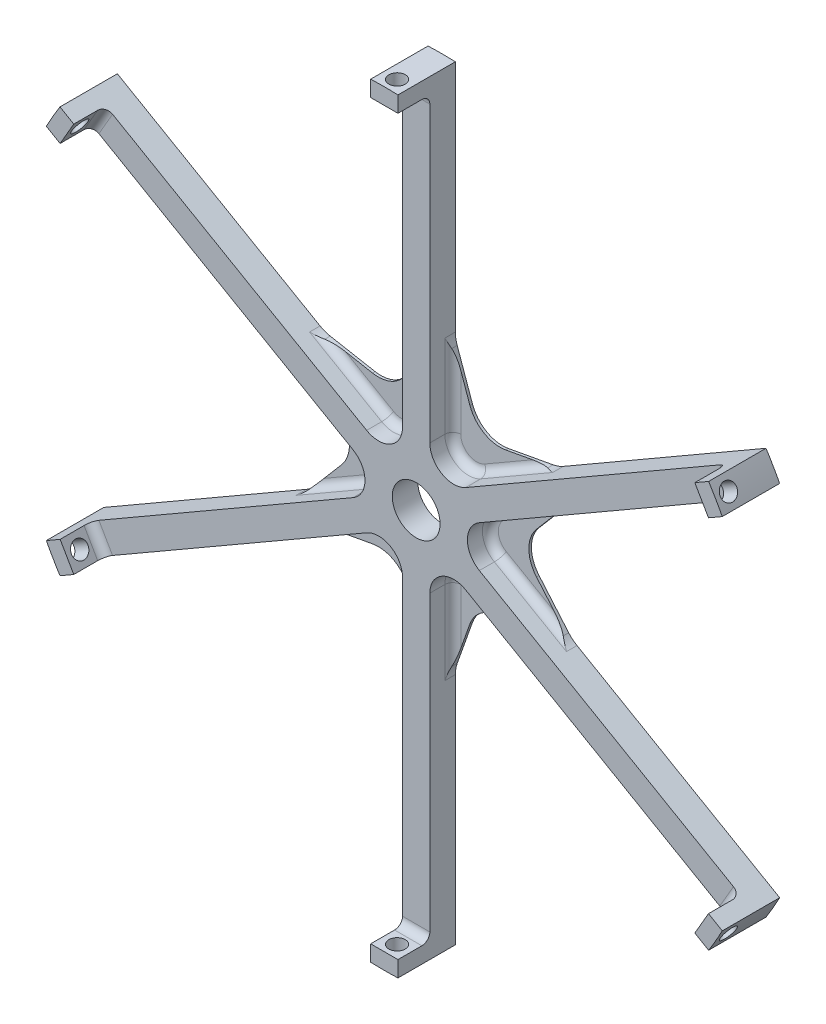
SolidWorks part; units mm, degrees
material "6061-T6 (SS)"
ref_plane "Front" through (0, 0, 0) normal (0, 0, 1) x (1, 0, 0)
ref_plane "Top" through (0, 0, 0) normal (0, 1, 0) x (1, 0, 0)
ref_plane "Right" through (0, 0, 0) normal (1, 0, 0) x (0, 0, -1)
sketch "Sketch1" plane through (0, 0, 0) normal (0, 0, 1) x (1, 0, 0)
  circle A0 centre (0, 0) radius 76.2
  dimension "D1" = 152.4
extrude "Boss-Extrude1" add sketch "Sketch1" along normal blind 11.43
sketch "Sketch3" plane through (0, 0, 11.43) normal (0, 0, 1) x (1, 0, 0)
  circle A0 centre (0, 0) radius 4.7625
  dimension "D1" = 9.525
extrude "Cut-Extrude2" cut sketch "Sketch3" against normal through all
sketch "Sketch2" plane through (0, 0, 11.43) normal (0, 0, 1) x (1, 0, 0)
  line L0 (0, 0) -> (0, 76.2) construction
  line L1 (0, 0) -> (-65.9911, 38.1) construction
  line L2 (-2.7178, 12.9563) -> (-2.7178, 76.2)
  line L3 (-9.8615, 8.8318) -> (-64.6322, 40.4537)
  line L4 (2.7178, -4.7074) -> (2.7178, 76.2)
  line L5 (2.7178, -4.7074) -> (-67.35, 35.7463)
  line L6 (-2.7178, 4.7074) -> (-2.7178, 76.2) construction
  line L7 (-2.7178, 4.7074) -> (-64.6322, 40.4537) construction
  circle A0 centre (0, 0) radius 76.2 construction
  circle A1 centre (0, 0) radius 7.9375
  arc A2 (-2.7178, 12.9563) -> (-9.8615, 8.8318) centre (-7.4803, 12.9563) cw
  circle M1 centre (0, 0) radius 76.2
  dimension "D1" = 15.875
  dimension "D5" = 4.7625
  dimension "D2" = 60
  dimension "D3" = 2.7178
  dimension "D4" = 2.7178
extrude "Cut-Extrude1" cut sketch "Sketch2" against normal through all contours A1 L2 L3 M1 region at (-25.4311, 44.0479, 11.43)
pattern_circular "CirPattern1" count 6 over 360 about axis through (0, 0, 11.43) along (0, 0, -1) of "Cut-Extrude1"
sketch "Sketch4" plane through (0, 0, 11.43) normal (0, 0, 1) x (1, 0, 0)
  line L0 (0, 0) -> (0, 73.025) construction
  line L1 (-9.8615, 8.8318) -> (-64.5902, 40.4294) construction
  line L2 (-12.5793, 4.1244) -> (-67.308, 35.7221) construction
  line L3 (-2.7178, 12.9563) -> (-2.7178, 76.1515) construction
  line L4 (2.7178, 12.9563) -> (2.7178, 76.1515) construction
  line L5 (9.8615, 8.8318) -> (64.5902, 40.4294) construction
  line L6 (12.5793, 4.1244) -> (67.308, 35.7221) construction
  line L7 (2.7178, -12.9563) -> (2.7178, -76.1515) construction
  line L8 (-9.8616, -8.8318) -> (-64.5902, -40.4294) construction
  line L9 (-12.5794, -4.1244) -> (-67.308, -35.7221) construction
  line L10 (-2.7178, -12.9563) -> (-2.7178, -76.1515) construction
  line L11 (9.8615, -8.8318) -> (64.5902, -40.4294) construction
  line L12 (12.5793, -4.1244) -> (67.308, -35.7221) construction
  line L13 (-9.8615, 8.8318) -> (-64.5902, 40.4294)
  line L14 (-12.5793, 4.1244) -> (-67.308, 35.7221)
  line L15 (-2.7178, 12.9563) -> (-2.7178, 76.1515)
  line L16 (2.7178, 12.9563) -> (2.7178, 76.1515)
  line L17 (9.8615, 8.8318) -> (64.5902, 40.4294)
  line L18 (12.5793, 4.1244) -> (67.308, 35.7221)
  line L19 (2.7178, -12.9563) -> (2.7178, -76.1515)
  line L20 (-9.8616, -8.8318) -> (-64.5902, -40.4294)
  line L21 (-12.5794, -4.1244) -> (-67.308, -35.7221)
  line L22 (-2.7178, -12.9563) -> (-2.7178, -76.1515)
  line L23 (9.8615, -8.8318) -> (64.5902, -40.4294)
  line L24 (12.5793, -4.1244) -> (67.308, -35.7221)
  line L25 (2.7178, 72.9744) -> (-2.7178, 72.9744)
  line L26 (-61.8388, 38.8409) -> (-64.5566, 34.1335)
  line L27 (-64.5566, -34.1335) -> (-61.8388, -38.8409)
  line L28 (-2.7178, -72.9744) -> (2.7178, -72.9744)
  line L29 (61.8388, -38.8409) -> (64.5566, -34.1335)
  line L30 (61.8388, 38.8409) -> (64.5566, 34.1335)
  circle A0 centre (0, 0) radius 73.025
  line M4 (-12.5794, -4.1244) -> (-67.308, -35.7221)
  line M8 (-2.7178, -12.9563) -> (-2.7178, -76.1515)
  line M12 (9.8615, -8.8318) -> (64.5902, -40.4294)
  line M16 (12.5793, 4.1244) -> (67.308, 35.7221)
  line M20 (2.7178, 12.9563) -> (2.7178, 76.1515)
  line M24 (-9.8615, 8.8318) -> (-64.5902, 40.4294)
  circle M26 centre (0, 0) radius 4.7625
  dimension "D1" = 146.05
extrude "Cut-Extrude3" cut sketch "Sketch4" against normal blind 6.35 contours L25 L15 L26 L14 L27 L20 L28 L19 L29 L24 L30 L17 M26 M24 M4 M8 M12 M16 M20 region at (35.4801, 61.4534, 11.43)
hole_wizard "#30 (0.1285) Diameter Hole1" positions "3DSketch1" profile "Sketch5" hole size "#30" standard "ANSI Inch"
sketch3d "3DSketch1"
  point P0 (0, 76.2, 8.89)
  dimension "D1" = 2.54
sketch "Sketch5" plane through (0, 76.2, 8.89) normal (1, 0, 0) x (0, 0, 1)
  line L0 (0, 0) -> (0, 39.0806)
  line L1 (0, 39.0806) -> (1.6319, 38.1)
  line L2 (1.6319, 38.1) -> (1.6319, 0)
  line L5 (1.6319, 0) -> (0, 0)
  line L10 (0, 39.0806) -> (-1.632, 38.1) construction
  line L11 (0, -6.35) -> (0, 107.95) construction
  dimension "Hole Dia." = 3.2639
  dimension "Hole Depth" = 38.1
  dimension "Drill Angle" = 118
pattern_circular "CirPattern2" count 6 over 360 about axis through (0, 0, 11.43) along (0, 0, -1) of "#30 (0.1285) Diameter Hole1"
fillet "Fillet3" radius 1.5875 6 edges at (-63.1977, 36.4872, 5.08) (0, 72.9744, 5.08) (63.1977, 36.4872, 5.08) (63.1977, -36.4872, 5.08) (0, -72.9744, 5.08) (-63.1977, -36.4872, 5.08)
sketch "Sketch7" plane through (0, 0, 0) normal (0, 0, -1) x (-1, 0, 0)
  line L0 (-12.5793, 4.1244) -> (-67.308, 35.7221) construction
  line L1 (-12.5793, -4.1244) -> (-67.308, -35.7221) construction
  line L2 (-25.9934, -11.869) -> (-15.875, 0)
  line L3 (-15.875, 0) -> (-25.9934, 11.869)
  line L4 (-9.8615, -8.8318) -> (-64.5902, -40.4294) construction
  line L5 (-2.7178, -12.9563) -> (-2.7178, -76.1515) construction
  line L6 (2.7178, -12.9563) -> (2.7178, -76.1515) construction
  line L7 (9.8616, -8.8318) -> (64.5902, -40.4294) construction
  line L8 (-12.5793, -4.1244) -> (-67.308, -35.7221)
  line L9 (-12.5793, 4.1244) -> (-67.308, 35.7221)
  line L10 (12.5794, -4.1244) -> (67.308, -35.7221) construction
  line L11 (12.5793, 4.1244) -> (67.308, 35.7221) construction
  line L12 (9.8615, 8.8318) -> (64.5902, 40.4294) construction
  line L13 (2.7178, 12.9563) -> (2.7178, 76.1515) construction
  line L14 (-2.7178, 12.9563) -> (-2.7178, 76.1515) construction
  line L15 (-9.8615, 8.8318) -> (-64.5902, 40.4294) construction
  line L16 (-9.8615, -8.8318) -> (-64.5902, -40.4294)
  line L17 (-2.7178, -12.9563) -> (-2.7178, -76.1515)
  line L18 (2.7178, -12.9563) -> (2.7178, -76.1515)
  line L19 (9.8616, -8.8318) -> (64.5902, -40.4294)
  line L20 (12.5794, -4.1244) -> (67.308, -35.7221)
  line L21 (12.5793, 4.1244) -> (67.308, 35.7221)
  line L22 (9.8615, 8.8318) -> (64.5902, 40.4294)
  line L23 (2.7178, 12.9563) -> (2.7178, 76.1515)
  line L24 (-2.7178, 12.9563) -> (-2.7178, 76.1515)
  line L25 (-9.8615, 8.8318) -> (-64.5902, 40.4294)
  line L26 (0, 0) -> (-37.8206, 0) construction
  line L27 (0, 0) -> (-18.9103, 32.7536) construction
  line L28 (0, 0) -> (18.9103, 32.7536) construction
  line L29 (0, 0) -> (37.8206, 0) construction
  line L30 (0, 0) -> (18.9103, -32.7536) construction
  line L31 (0, 0) -> (-18.9103, -32.7536) construction
  line L32 (-23.2756, -16.5764) -> (-7.9375, -13.7482)
  line L33 (-7.9375, -13.7482) -> (-2.7178, -28.4455)
  line L34 (-23.2756, 16.5764) -> (-7.9375, 13.7482)
  line L35 (-7.9375, 13.7482) -> (-2.7178, 28.4455)
  line L36 (2.7178, 28.4455) -> (7.9375, 13.7482)
  line L37 (7.9375, 13.7482) -> (23.2756, 16.5764)
  line L38 (25.9934, 11.869) -> (15.875, 0)
  line L39 (15.875, 0) -> (25.9934, -11.869)
  line L40 (23.2756, -16.5764) -> (7.9375, -13.7482)
  line L41 (7.9375, -13.7482) -> (2.7178, -28.4455)
  circle A0 centre (0, 0) radius 28.575
  circle A1 centre (0, 0) radius 4.7625
  arc A2 (2.7178, 12.9563) -> (9.8615, 8.8318) centre (7.4803, 12.9563) ccw construction
  arc A3 (12.5793, 4.1244) -> (12.5794, -4.1244) centre (14.9606, 0) ccw construction
  arc A4 (9.8616, -8.8318) -> (2.7178, -12.9563) centre (7.4803, -12.9563) ccw construction
  arc A5 (-2.7178, -12.9563) -> (-9.8615, -8.8318) centre (-7.4803, -12.9563) ccw construction
  arc A6 (-12.5793, -4.1244) -> (-12.5793, 4.1244) centre (-14.9606, 0) ccw construction
  arc A7 (-9.8615, 8.8318) -> (-2.7178, 12.9563) centre (-7.4803, 12.9563) ccw construction
  circle A8 centre (0, 0) radius 15.875
  arc A14 (-9.8615, 8.8318) -> (-2.7178, 12.9563) centre (-7.4803, 12.9563) ccw
  arc A15 (-12.5793, -4.1244) -> (-12.5793, 4.1244) centre (-14.9606, 0) ccw
  arc A16 (-2.7178, -12.9563) -> (-9.8615, -8.8318) centre (-7.4803, -12.9563) ccw
  arc A17 (9.8616, -8.8318) -> (2.7178, -12.9563) centre (7.4803, -12.9563) ccw
  arc A18 (12.5793, 4.1244) -> (12.5794, -4.1244) centre (14.9606, 0) ccw
  arc A19 (2.7178, 12.9563) -> (9.8615, 8.8318) centre (7.4803, 12.9563) ccw
  point P47 (0, 0)
  line M2 (67.308, -35.7221) -> (12.5794, -4.1244)
  arc M3 (12.5794, -4.1244) -> (12.5793, 4.1244) centre (14.9606, 0) cw
  line M4 (12.5793, 4.1244) -> (67.308, 35.7221)
  line M6 (64.5902, 40.4294) -> (9.8615, 8.8318)
  arc M7 (9.8615, 8.8318) -> (2.7178, 12.9563) centre (7.4803, 12.9563) cw
  line M8 (2.7178, 12.9563) -> (2.7178, 76.1515)
  line M10 (-2.7178, 76.1515) -> (-2.7178, 12.9563)
  arc M11 (-2.7178, 12.9563) -> (-9.8615, 8.8318) centre (-7.4803, 12.9563) cw
  line M12 (-9.8615, 8.8318) -> (-64.5902, 40.4294)
  line M14 (-67.308, 35.7221) -> (-12.5793, 4.1244)
  arc M15 (-12.5793, 4.1244) -> (-12.5793, -4.1244) centre (-14.9606, 0) cw
  line M16 (-12.5793, -4.1244) -> (-67.308, -35.7221)
  line M18 (-64.5902, -40.4294) -> (-9.8615, -8.8318)
  arc M19 (-9.8615, -8.8318) -> (-2.7178, -12.9563) centre (-7.4803, -12.9563) cw
  line M20 (-2.7178, -12.9563) -> (-2.7178, -76.1515)
  line M22 (2.7178, -76.1515) -> (2.7178, -12.9563)
  arc M23 (2.7178, -12.9563) -> (9.8616, -8.8318) centre (7.4803, -12.9563) cw
  line M24 (9.8616, -8.8318) -> (64.5902, -40.4294)
  dimension "D1" = 57.15
  dimension "D2" = 31.75
  dimension "D3" = 6
extrude "Boss-Extrude2" add sketch "Sketch7" against normal blind 0.508 contours A8 L22 L37 | A8 L36 L23 | A8 M6 M8 M7 | A8 M4 M3 M2 | A8 L38 L21 | A8 L20 L39 | A8 L40 L19 | A8 M22 M24 M23 | A8 L18 L41 | A8 L33 L17 | A8 M18 M20 M19 | A8 L16 L32 | L9 A8 M16 M15 | A8 L2 L8 | A8 L3 M14 | A8 L34 L25 | A8 M10 M12 M11 | A8 L24 L35 region at (19.0201, -5.863, 0) region at (19.0201, 5.863, 0) region at (13.3372, 0, 0) region at (14.5876, -13.5403, 0) region at (6.6686, -11.5504, 0) region at (14.5876, 13.5403, 0) region at (4.4325, -19.4034, 0) region at (6.6686, 11.5504, 0) region at (4.4325, 19.4034, 0) region at (-4.4325, -19.4034, 0) region at (-4.4325, 19.4034, 0) region at (-6.6686, -11.5504, 0) region at (-14.5876, -13.5403, 0) region at (-6.6686, 11.5504, 0) region at (-14.5876, 13.5403, 0) region at (-19.0201, -5.863, 0) region at (-19.0201, 5.863, 0) region at (-13.3372, 0, 0)
fillet "Fillet5" radius 6.35 18 edges at (-25.9934, 11.869, 0.254) (-25.9934, -11.869, 0.254) (-23.2756, -16.5764, 0.254) (-2.7178, -28.4455, 0.254) (2.7178, -28.4455, 0.254) (23.2756, -16.5764, 0.254) (25.9934, -11.869, 0.254) (25.9934, 11.869, 0.254) (23.2756, 16.5764, 0.254) (2.7178, 28.4455, 0.254) (-2.7178, 28.4455, 0.254) (-23.2756, 16.5764, 0.254) (7.9375, -13.7482, 0.254) (-7.9375, -13.7482, 0.254) (-15.875, 0, 0.254) (-7.9375, 13.7482, 0.254) (7.9375, 13.7482, 0.254) (15.875, 0, 0.254)
fillet "Fillet6" radius 1.5875 18 edges at (17.0423, -12.9776, 0.508) (2.7178, -21.2479, 0.508) (19.7601, 8.2703, 0.508) (19.7601, -8.2703, 0.508) (17.0423, 12.9776, 0.508) (5.099, 8.8318, 0.508) (-17.0423, 12.9776, 0.508) (-5.099, 8.8318, 0.508) (5.099, -8.8318, 0.508) (10.1981, 0, 0.508) (2.7178, 21.2479, 0.508) (-2.7178, 21.2479, 0.508) (-19.7601, 8.2703, 0.508) (-10.1981, 0, 0.508) (-19.7601, -8.2703, 0.508) (-17.0423, -12.9776, 0.508) (-5.0991, -8.8318, 0.508) (-2.7178, -21.2479, 0.508)
ref_plane "Plane1" through (0, 0, 11.43) normal (0, 0, 1) x (1, 0, 0)
sketch "Sketch8" plane through (0, 0, 11.43) normal (0, 0, 1) x (1, 0, 0)
  line L0 (0, 0) -> (0, -100.646) construction
  line L1 (0, 0) -> (-144.2758, 0) construction
  line L2 (-82.55, -82.55) -> (-82.55, 22.2422) construction
  line L3 (-82.55, -82.55) -> (30.6723, -82.55) construction
  line L4 (-63.1818, -33.3398) -> (-60.464, -38.0471) construction
  line L5 (-63.1818, -33.3398) -> (-60.464, -38.0471)
  line L6 (-61.8388, 38.8409) -> (-64.5566, 34.1335) construction
  line L7 (2.7178, 72.9744) -> (-2.7178, 72.9744) construction
  line L8 (61.8388, 38.8409) -> (64.5566, 34.1335) construction
  line L9 (61.8388, -38.8409) -> (64.5566, -34.1335) construction
  line L10 (-2.7178, -72.9744) -> (2.7178, -72.9744) construction
  line L11 (-64.5566, -34.1335) -> (-61.8388, -38.8409) construction
  line L12 (-61.8388, 38.8409) -> (-64.5566, 34.1335)
  line L13 (2.7178, 72.9744) -> (-2.7178, 72.9744)
  line L14 (61.8388, 38.8409) -> (64.5566, 34.1335)
  line L15 (61.8388, -38.8409) -> (64.5566, -34.1335)
  line L16 (-2.7178, -72.9744) -> (2.7178, -72.9744)
  line L17 (-64.5566, -34.1335) -> (-61.8388, -38.8409)
  line L18 (-84.2636, 0) -> (-42.1318, -72.9744)
  line L19 (-42.1318, -72.9744) -> (42.1318, -72.9744)
  line L20 (42.1318, -72.9744) -> (84.2636, 0)
  line L21 (84.2636, 0) -> (42.1318, 72.9744)
  line L22 (42.1318, 72.9744) -> (-42.1318, 72.9744)
  line L23 (-42.1318, 72.9744) -> (-84.2636, 0)
  circle A0 centre (0, 0) radius 71.3869
  point P0 (0, 0)
  point P1 (-82.55, -82.55)
  dimension "D1" = 82.55
  dimension "D2" = 82.55
